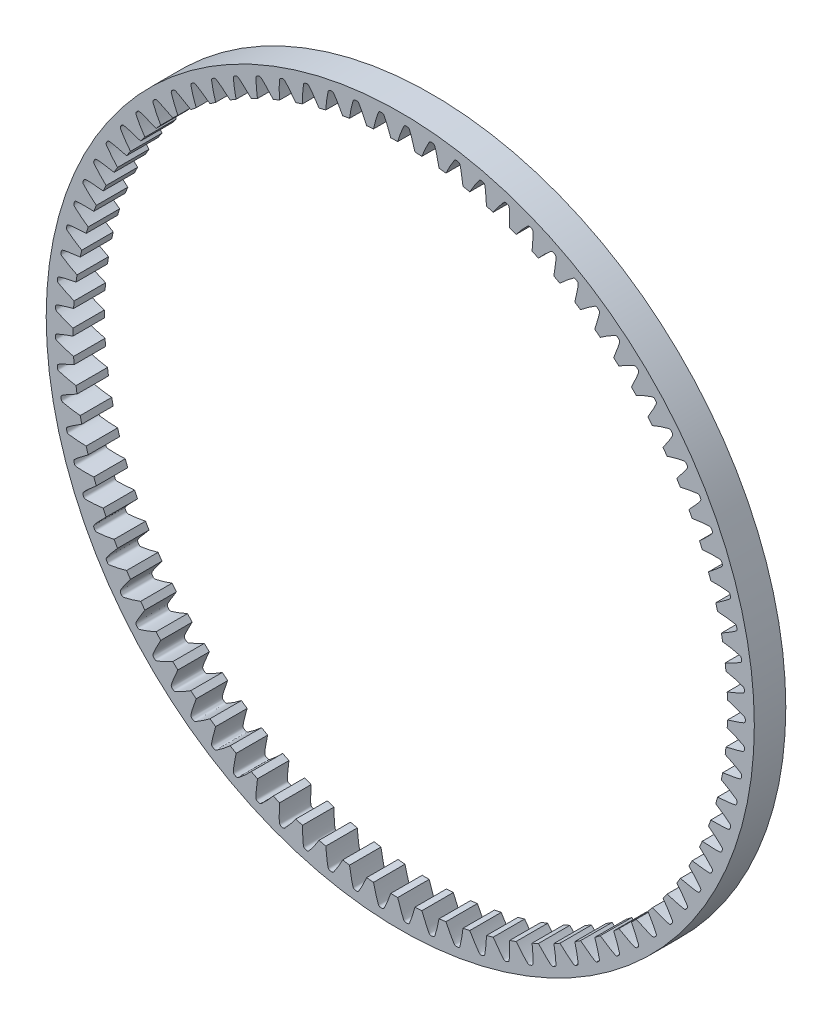
SolidWorks part; units mm, degrees
ref_plane "Front Plane" through (0, 0, 0) normal (0, 0, 1) x (1, 0, 0)
ref_plane "Top Plane" through (0, 0, 0) normal (0, 1, 0) x (1, 0, 0)
ref_plane "Right Plane" through (0, 0, 0) normal (1, 0, 0) x (0, 0, -1)
ref_axis "Axis1" through (0, 0, 55) along (0, 0, -1)
sketch "SketchRevolveSpurGear" plane through (0, 0, 0) normal (1, 0, 0) x (0, 0, -1)
  line L0 (0, 0) -> (1, 0) construction
  line L1 (-2, 41.6) -> (-2, 45)
  line L2 (-2, 45) -> (2, 45)
  line L3 (2, 45) -> (2, 41.6)
  line L4 (2, 41.6) -> (-2, 41.6)
  dimension "Side1" = 2
  dimension "OutsideRadius" = 45
  dimension "Side2" = 2
  dimension "MinorDiameter" = 41.6
revolve "SpurGear" add sketch "SketchRevolveSpurGear" angle 360 about L0
sketch "SketchToothSpurGear" plane through (0, 0, 0) normal (0, 0, 1) x (1, 0, 0)
  arc A0 (41.5528, -1.1056) -> (41.5528, 1.1056) centre (0, 0) ccw
  spline S0 degree 3 poles (41.5528, 1.1056) (41.6733, 1.0743) (41.8577, 1.0231) (42.1081, 0.9476) (42.3084, 0.8838) (42.5167, 0.8139) (42.7328, 0.7377) (42.9564, 0.6546) (43.1884, 0.5663) (43.4375, 0.4582) (43.6357, 0.3965) (43.7445, 0.3195) (43.7756, 0.2888) (43.802, 0.2542) (43.8231, 0.216) (43.8437, 0.162) (43.8509, 0.1036) (43.8498, 0.0451) (43.8501, 0) (43.8498, -0.0451) (43.8509, -0.1036) (43.8437, -0.162) (43.8231, -0.216) (43.802, -0.2542) (43.7756, -0.2888) (43.7445, -0.3195) (43.6357, -0.3965) (43.4375, -0.4582) (43.1884, -0.5663) (42.9564, -0.6546) (42.7328, -0.7377) (42.5167, -0.8139) (42.3084, -0.8838) (42.1081, -0.9476) (41.8577, -1.0231) (41.6733, -1.0743) (41.5528, -1.1056) knots 0 0 0 0 0.069601 0.10704 0.14624 0.187199 0.229918 0.274396 0.320634 0.368631 0.426701 0.434807 0.442914 0.451021 0.459128 0.467235 0.483178 0.491589 0.5 0.508411 0.516822 0.532765 0.540872 0.548979 0.557086 0.565193 0.573299 0.631369 0.679366 0.725604 0.770082 0.812801 0.85376 0.89296 0.930399 1 1 1 1
extrude "ToothExtrudeCutSpurGear" cut sketch "SketchToothSpurGear" against normal blind 2 and the other way blind 2
pattern_circular "PatternSpurGear" count 85 every 4.235 about axis through (0, 0, 55) along (0, 0, -1) of "ToothExtrudeCutSpurGear"
sketch "AuxiliarySketchSpurGear" plane through (0, 0, 0) normal (0, 0, 1) x (1, 0, 0)
  circle A0 centre (0, 0) radius 42.5 construction
  circle A1 centre (0, 0) radius 39.9369 construction
  circle A2 centre (0, 0) radius 43.85 construction
  circle A3 centre (0, 0) radius 41.6 construction
  dimension "PitchDiameter" = 85
  dimension "BaseDiameter" = 79.8739
  dimension "MajorDiameter" = 87.7
  dimension "MinorDiameter" = 83.2
